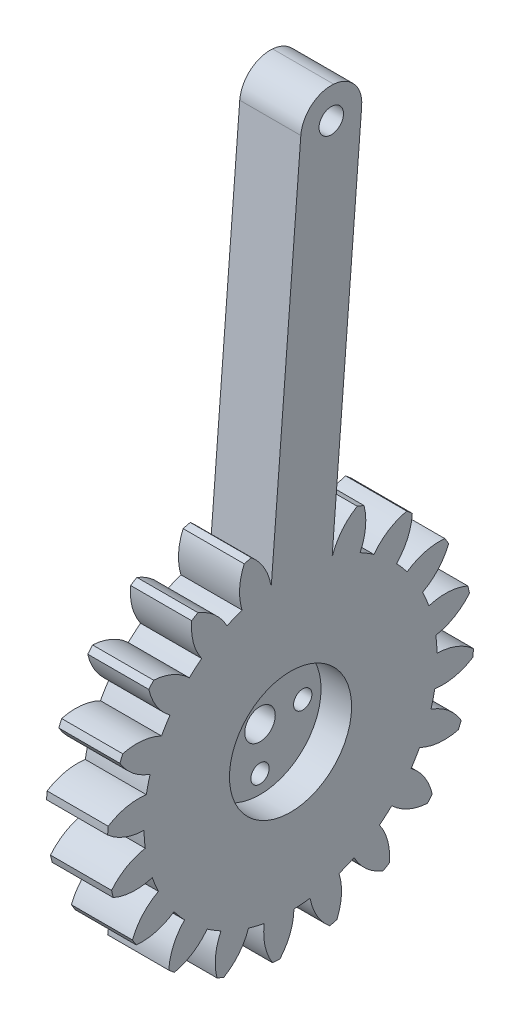
SolidWorks part; units mm, degrees
ref_plane "前视基准面" through (0, 0, 0) normal (0, 0, 1) x (1, 0, 0)
ref_plane "上视基准面" through (0, 0, 0) normal (0, 1, 0) x (1, 0, 0)
ref_plane "右视基准面" through (0, 0, 0) normal (1, 0, 0) x (0, 0, -1)
other "Configuration Table"
sketch "草图1" plane through (0, 0, 0) normal (1, 0, 0) x (0, 0, -1)
  line L0 (0, 0) -> (50000, 0) construction
  line L1 (0, 27) -> (0, -50000) construction
  line L2 (0, 0) -> (8.2085, 22.5526) construction
  line L3 (0, 0) -> (3922.9548, 49845.8667) construction
  arc A0 (-7.9429, 22.6475) -> (-10.3978, 21.6307) centre (0, 0) ccw
  arc A5 (1.751, 29.9489) -> (-0.5557, 23.9936) centre (8.6776, 23.8416) ccw
  arc A6 (2.9556, 29.8541) -> (4.3022, 23.6112) centre (-4.8411, 24.9056) cw
  arc A7 (2.9556, 29.8541) -> (1.751, 29.9489) centre (0, 0) ccw
  arc A8 (12.0363, 27.4796) -> (11.3879, 21.1262) centre (3.092, 25.1826) cw
  arc A9 (12.0363, 27.4796) -> (10.92, 27.942) centre (0, 0) ccw
  arc A10 (10.92, 27.942) -> (6.886, 22.9909) centre (15.6204, 19.9932) ccw
  arc A11 (19.9389, 22.4152) -> (17.3589, 16.5731) centre (10.7225, 22.9946) cw
  arc A12 (19.9389, 22.4152) -> (19.0201, 23.1999) centre (0, 0) ccw
  arc A13 (19.0201, 23.1999) -> (13.6535, 19.7378) centre (21.0341, 14.1877) ccw
  arc A14 (25.8897, 15.1566) -> (21.6307, 10.3978) centre (17.3035, 18.5557) cw
  arc A15 (25.8897, 15.1566) -> (25.2583, 16.1869) centre (0, 0) ccw
  arc A16 (25.2583, 16.1869) -> (19.0846, 14.5526) centre (24.3888, 6.9934) ccw
  arc A17 (29.3062, 6.4145) -> (23.7851, 3.2046) centre (22.1906, 12.3004) cw
  arc A18 (29.3062, 6.4145) -> (29.0241, 7.5894) centre (0, 0) ccw
  arc A19 (29.0241, 7.5894) -> (22.6475, 7.9429) centre (25.3562, -0.8855) ccw
  arc A20 (29.8541, -2.9556) -> (23.6112, -4.3022) centre (24.9056, 4.8411) cw
  arc A21 (29.8541, -2.9556) -> (29.9489, -1.751) centre (0, 0) ccw
  arc A22 (29.9489, -1.751) -> (23.9936, 0.5557) centre (23.8416, -8.6776) ccw
  arc A23 (27.4796, -12.0363) -> (21.1262, -11.3879) centre (25.1826, -3.092) cw
  arc A24 (27.4796, -12.0363) -> (27.942, -10.92) centre (0, 0) ccw
  arc A25 (27.942, -10.92) -> (22.9909, -6.886) centre (19.9932, -15.6204) ccw
  arc A26 (22.4152, -19.9389) -> (16.5731, -17.3589) centre (22.9946, -10.7225) cw
  arc A27 (22.4152, -19.9389) -> (23.1999, -19.0201) centre (0, 0) ccw
  arc A28 (23.1999, -19.0201) -> (19.7378, -13.6535) centre (14.1877, -21.0341) ccw
  arc A29 (15.1566, -25.8897) -> (10.3978, -21.6307) centre (18.5557, -17.3035) cw
  arc A30 (15.1566, -25.8897) -> (16.1869, -25.2583) centre (0, 0) ccw
  arc A31 (16.1869, -25.2583) -> (14.5526, -19.0846) centre (6.9934, -24.3888) ccw
  arc A32 (6.4145, -29.3062) -> (3.2046, -23.7851) centre (12.3004, -22.1906) cw
  arc A33 (6.4145, -29.3062) -> (7.5894, -29.0241) centre (0, 0) ccw
  arc A34 (7.5894, -29.0241) -> (7.9429, -22.6475) centre (-0.8855, -25.3562) ccw
  arc A35 (-2.9556, -29.8541) -> (-4.3022, -23.6112) centre (4.8411, -24.9056) cw
  arc A36 (-2.9556, -29.8541) -> (-1.751, -29.9489) centre (0, 0) ccw
  arc A37 (-1.751, -29.9489) -> (0.5557, -23.9936) centre (-8.6776, -23.8416) ccw
  arc A38 (-12.0363, -27.4796) -> (-11.3879, -21.1262) centre (-3.092, -25.1826) cw
  arc A39 (-12.0363, -27.4796) -> (-10.92, -27.942) centre (0, 0) ccw
  arc A40 (-10.92, -27.942) -> (-6.886, -22.9909) centre (-15.6204, -19.9932) ccw
  arc A41 (-19.9389, -22.4152) -> (-17.3589, -16.5731) centre (-10.7225, -22.9946) cw
  arc A42 (-19.9389, -22.4152) -> (-19.0201, -23.1999) centre (0, 0) ccw
  arc A43 (-19.0201, -23.1999) -> (-13.6535, -19.7378) centre (-21.0341, -14.1877) ccw
  arc A44 (-25.8897, -15.1566) -> (-21.6307, -10.3978) centre (-17.3035, -18.5557) cw
  arc A45 (-25.8897, -15.1566) -> (-25.2583, -16.1869) centre (0, 0) ccw
  arc A46 (-25.2583, -16.1869) -> (-19.0846, -14.5526) centre (-24.3888, -6.9934) ccw
  arc A47 (-29.3062, -6.4145) -> (-23.7851, -3.2046) centre (-22.1906, -12.3004) cw
  arc A48 (-29.3062, -6.4145) -> (-29.0241, -7.5894) centre (0, 0) ccw
  arc A49 (-29.0241, -7.5894) -> (-22.6475, -7.9429) centre (-25.3562, 0.8855) ccw
  arc A50 (-29.8541, 2.9556) -> (-23.6112, 4.3022) centre (-24.9056, -4.8411) cw
  arc A51 (-29.8541, 2.9556) -> (-29.9489, 1.751) centre (0, 0) ccw
  arc A52 (-29.9489, 1.751) -> (-23.9936, -0.5557) centre (-23.8416, 8.6776) ccw
  arc A53 (-27.4796, 12.0363) -> (-21.1262, 11.3879) centre (-25.1826, 3.092) cw
  arc A54 (-27.4796, 12.0363) -> (-27.942, 10.92) centre (0, 0) ccw
  arc A55 (-27.942, 10.92) -> (-22.9909, 6.886) centre (-19.9932, 15.6204) ccw
  arc A56 (-22.4152, 19.9389) -> (-16.5731, 17.3589) centre (-22.9946, 10.7225) cw
  arc A57 (-22.4152, 19.9389) -> (-23.1999, 19.0201) centre (0, 0) ccw
  arc A58 (-23.1999, 19.0201) -> (-19.7378, 13.6535) centre (-14.1877, 21.0341) ccw
  arc A59 (-15.1566, 25.8897) -> (-10.3978, 21.6307) centre (-18.5557, 17.3035) cw
  arc A60 (-15.1566, 25.8897) -> (-16.1869, 25.2583) centre (0, 0) ccw
  arc A61 (-16.1869, 25.2583) -> (-14.5526, 19.0846) centre (-6.9934, 24.3888) ccw
  arc A62 (-6.4145, 29.3062) -> (-3.2046, 23.7851) centre (-12.3004, 22.1906) cw
  arc A63 (-6.4145, 29.3062) -> (-7.5894, 29.0241) centre (0, 0) ccw
  arc A64 (-7.5894, 29.0241) -> (-7.9429, 22.6475) centre (0.8855, 25.3562) ccw
  arc A65 (-14.5526, 19.0846) -> (-16.5731, 17.3589) centre (0, 0) ccw
  arc A66 (-19.7378, 13.6535) -> (-21.1262, 11.3879) centre (0, 0) ccw
  arc A67 (-22.9909, 6.886) -> (-23.6112, 4.3022) centre (0, 0) ccw
  arc A68 (-23.9936, -0.5557) -> (-23.7851, -3.2046) centre (0, 0) ccw
  arc A69 (-19.0846, -14.5526) -> (-17.3589, -16.5731) centre (0, 0) ccw
  arc A70 (-22.6475, -7.9429) -> (-21.6307, -10.3978) centre (0, 0) ccw
  arc A71 (-13.6535, -19.7378) -> (-11.3879, -21.1262) centre (0, 0) ccw
  arc A72 (0.5557, -23.9936) -> (3.2046, -23.7851) centre (0, 0) ccw
  arc A73 (7.9429, -22.6475) -> (10.3978, -21.6307) centre (0, 0) ccw
  arc A74 (14.5526, -19.0846) -> (16.5731, -17.3589) centre (0, 0) ccw
  arc A75 (19.7378, -13.6535) -> (21.1262, -11.3879) centre (0, 0) ccw
  arc A76 (22.9909, -6.886) -> (23.6112, -4.3022) centre (0, 0) ccw
  arc A77 (23.9936, 0.5557) -> (23.7851, 3.2046) centre (0, 0) ccw
  arc A78 (22.6475, 7.9429) -> (21.6307, 10.3978) centre (0, 0) ccw
  arc A79 (19.0846, 14.5526) -> (17.3589, 16.5731) centre (0, 0) ccw
  arc A80 (13.6535, 19.7378) -> (11.3879, 21.1262) centre (0, 0) ccw
  arc A81 (6.886, 22.9909) -> (4.3022, 23.6112) centre (0, 0) ccw
  arc A82 (-0.5557, 23.9936) -> (-3.2046, 23.7851) centre (0, 0) ccw
  arc A83 (-6.886, -22.9909) -> (-4.3022, -23.6112) centre (0, 0) ccw
  point P134 (0, 0)
  dimension "D1" = 48
  dimension "D3" = 20
  dimension "D2" = 20
  dimension "D5" = 4.5
extrude "凸台-拉伸1" add sketch "草图1" along normal blind 10
sketch "草图2" plane through (10, 0, 0) normal (1, 0, 0) x (0, 0, -1)
  line L0 (0, 0) -> (0, 50000) construction
  line L5 (0, 0) -> (3922.9548, 49845.8667) construction
  line L6 (2.0767, 90.1149) -> (-4.9846, 0.3923)
  line L7 (-4.9846, 0.3923) -> (4.9846, -0.3923)
  line L8 (4.9846, -0.3923) -> (12.0459, 89.3303)
  line L9 (12.0459, 89.3303) -> (2.0767, 90.1149)
  dimension "D1" = 4.5
  dimension "D2" = 5
  dimension "D3" = 5
  dimension "D4" = 90
extrude "凸台-拉伸2" add sketch "草图2" against normal blind 10
fillet "圆角1" radius 5 2 edges at (5, 89.3303, -12.0459) (5, 90.1149, -2.0767)
sketch "草图3" plane through (10, 0, 0) normal (1, 0, 0) x (0, 0, -1)
  circle A0 centre (0, 0) radius 2.5
  dimension "D1" = 5
extrude "切除-拉伸1" cut sketch "草图3" against normal blind 10
sketch "草图4" plane through (10, 0, 0) normal (1, 0, 0) x (0, 0, -1)
  circle A0 centre (6.669, 84.738) radius 2
  dimension "D1" = 4
extrude "切除-拉伸2" cut sketch "草图4" against normal blind 10
sketch "草图5" plane through (10, 0, 0) normal (1, 0, 0) x (0, 0, -1)
  circle A0 centre (0, 0) radius 7 construction
  circle A1 centre (0, 7) radius 1.5
  circle A2 centre (7, 0) radius 1.5
  circle A3 centre (0, -7) radius 1.5
  circle A4 centre (-7, 0) radius 1.5
  point P14 (0, 0)
  dimension "D1" = 14
  dimension "D2" = 3
  dimension "D3" = 4
extrude "切除-拉伸3" cut sketch "草图5" against normal blind 10
sketch "草图6" plane through (10, 0, 0) normal (1, 0, 0) x (0, 0, -1)
  circle A0 centre (0, 0) radius 10
  dimension "D1" = 20
extrude "切除-拉伸4" cut sketch "草图6" against normal blind 5
